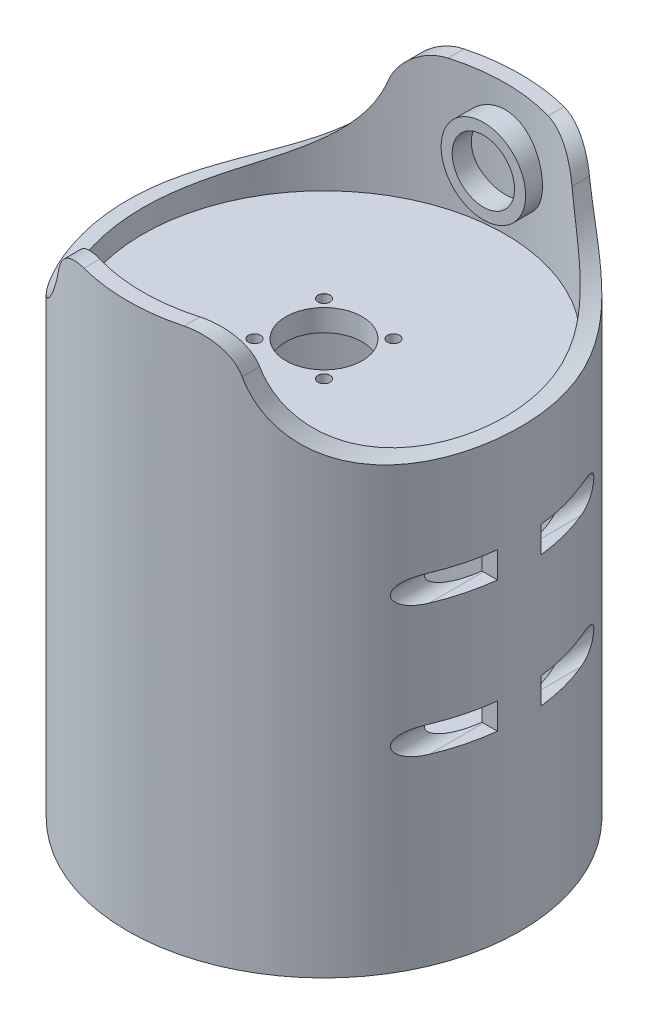
SolidWorks part; units mm, degrees
material "ABS"
ref_plane "Front Plane" through (0, 0, 0) normal (0, 0, 1) x (1, 0, 0)
ref_plane "Top Plane" through (0, 0, 0) normal (0, 1, 0) x (1, 0, 0)
ref_plane "Right Plane" through (0, 0, 0) normal (1, 0, 0) x (0, 0, -1)
sketch "Sketch7" plane through (0, 0, 0) normal (0, 1, 0) x (1, 0, 0)
  circle A0 centre (0, 0) radius 90
  point P0 (0, 0)
  dimension "D1" = 180
extrude "Boss-Extrude3" add sketch "Sketch7" along normal blind 250
sketch "Sketch8" plane through (0, 0, 0) normal (0, 0, 1) x (1, 0, 0)
  line L0 (-83, 210) -> (-83, 90) construction
  line L1 (83, 204) -> (83, 156) construction
  line L2 (90, 250) -> (-90, 250) construction
  line L3 (-90, 250) -> (-90, 0) construction
  line L4 (90, 0) -> (90, 250) construction
  line L5 (-83, 210) -> (-90, 210) construction
  line L6 (83, 210) -> (90, 210) construction
  line L7 (-83, 216) -> (-98, 216)
  line L8 (-98, 216) -> (-98, 204)
  line L9 (-98, 204) -> (-83, 204)
  line L10 (-83, 156) -> (-98, 156)
  line L11 (-98, 156) -> (-98, 144)
  line L12 (-98, 144) -> (-83, 144)
  line L13 (-83, 96) -> (-98, 96)
  line L14 (-98, 96) -> (-98, 84)
  line L15 (-98, 84) -> (-83, 84)
  line L17 (83, 216) -> (105.4044, 174.6914)
  line L18 (83, 204) -> (107.5565, 163.9943)
  line L19 (105.4044, 174.6914) -> (107.5565, 163.9943)
  line L21 (83, 156) -> (116.9139, 117.4845)
  line L22 (83, 144) -> (119.2158, 106.0432)
  line L23 (116.9139, 117.4845) -> (119.2158, 106.0432)
  line L25 (83, 96) -> (128.4235, 60.2777)
  line L26 (83, 84) -> (130.7254, 48.8363)
  line L27 (128.4235, 60.2777) -> (130.7254, 48.8363)
  line L28 (83, 144) -> (83, 96) construction
  arc A0 (-83, 204) -> (-83, 216) centre (-83, 210) ccw
  arc A1 (-83, 144) -> (-83, 156) centre (-83, 150) ccw
  arc A2 (-83, 84) -> (-83, 96) centre (-83, 90) ccw
  arc A3 (83, 216) -> (83, 204) centre (83, 210) ccw
  arc A4 (83, 156) -> (83, 144) centre (83, 150) ccw
  arc A5 (83, 96) -> (83, 84) centre (83, 90) ccw
  dimension "D4" = 12
  dimension "D1" = 40
  dimension "D2" = 7
  dimension "D3" = 15
  dimension "D5" = 40
  dimension "D6" = 60
  dimension "D7" = 60
  dimension "D8" = 60
  dimension "D9" = 15
shell "Shell3" thickness 7 removed face at (0, 250, 90) removed face at (0, 0, 90)
ref_plane "Plane1" through (0, 0, 83) normal (0, 0, -1) x (-1, 0, 0)
sketch "Sketch9" plane through (0, 0, 83) normal (0, 0, -1) x (-1, 0, 0)
  line L0 (83, 250) -> (-83, 250) construction
  circle A0 centre (0, 220) radius 19.3675
  circle A1 centre (0, 220) radius 14.2875
  dimension "D1" = 28.575
  dimension "D2" = 5.08
  dimension "D3" = 30
extrude "Boss-Extrude4" add sketch "Sketch9" along normal blind 10
mirror "Mirror1" about plane through (0, 0, 0) normal (0, 0, 1) of "Boss-Extrude4"
ref_plane "Plane2" through (0, 0, 10) normal (0, 0, 1) x (1, 0, 0)
sketch "Sketch11" plane through (0, 0, 10) normal (0, 0, 1) x (1, 0, 0)
  line L3 (-98, 96) -> (-98, 84)
  line L4 (-98, 84) -> (-83, 84)
  line L5 (-83, 96) -> (-98, 96)
  line L6 (-98, 96) -> (-98, 84)
  line L7 (-98, 84) -> (-83, 84)
  line L8 (-83, 96) -> (-98, 96)
  line L9 (-98, 156) -> (-98, 144)
  line L10 (-98, 144) -> (-83, 144)
  line L11 (-83, 156) -> (-98, 156)
  line L12 (-98, 156) -> (-98, 144)
  line L13 (-98, 144) -> (-83, 144)
  line L14 (-83, 156) -> (-98, 156)
  line L15 (-83, 216) -> (-98, 216)
  line L16 (-98, 216) -> (-98, 204)
  line L17 (-98, 204) -> (-83, 204)
  line L18 (-83, 216) -> (-98, 216)
  line L19 (-98, 216) -> (-98, 204)
  line L20 (-98, 204) -> (-83, 204)
  line L21 (128.4235, 60.2777) -> (83, 96)
  line L22 (130.7254, 48.8363) -> (128.4235, 60.2777)
  line L23 (83, 84) -> (130.7254, 48.8363)
  line L24 (115.4479, 96) -> (83, 96)
  line L25 (115.4479, 84) -> (115.4479, 96)
  line L26 (83, 84) -> (115.4479, 84)
  line L27 (116.9139, 117.4845) -> (83, 156)
  line L28 (119.2158, 106.0432) -> (116.9139, 117.4845)
  line L29 (83, 144) -> (119.2158, 106.0432)
  line L30 (113.0356, 156) -> (83, 156)
  line L31 (113.0356, 144) -> (113.0356, 156)
  line L32 (83, 144) -> (113.0356, 144)
  line L33 (105.4044, 174.6914) -> (83, 216)
  line L34 (83, 204) -> (107.5565, 163.9943)
  line L35 (107.5565, 163.9943) -> (105.4044, 174.6914)
  line L36 (119.1042, 216) -> (83, 216)
  line L37 (83, 204) -> (119.1042, 204)
  line L38 (119.1042, 204) -> (119.1042, 216)
  arc A1 (-83, 84) -> (-83, 96) centre (-83, 90) ccw
  arc A2 (-83, 84) -> (-83, 96) centre (-83, 90) ccw
  arc A3 (-83, 144) -> (-83, 156) centre (-83, 150) ccw
  arc A4 (-83, 144) -> (-83, 156) centre (-83, 150) ccw
  arc A5 (-83, 204) -> (-83, 216) centre (-83, 210) ccw
  arc A6 (-83, 204) -> (-83, 216) centre (-83, 210) ccw
  arc A7 (83, 96) -> (83, 84) centre (83, 90) ccw
  arc A8 (83, 96) -> (83, 84) centre (83, 90) ccw
  arc A9 (83, 156) -> (83, 144) centre (83, 150) ccw
  arc A10 (83, 156) -> (83, 144) centre (83, 150) ccw
  arc A11 (83, 216) -> (83, 204) centre (83, 210) ccw
  arc A12 (83, 216) -> (83, 204) centre (83, 210) ccw
  point P27 (115.4479, 96)
  point P32 (115.4479, 84)
  point P34 (113.0356, 156)
  point P36 (113.0356, 144)
  point P38 (115.4479, 216)
  point P41 (119.1042, 204)
  dimension "D1" = 0
  dimension "D2" = 0
  dimension "D3" = 0
  dimension "D4" = 0
  dimension "D5" = 0
  dimension "D6" = 0
extrude "Cut-Extrude3" cut sketch "Sketch11" along normal through all
mirror "Mirror2" about plane through (0, 0, 0) normal (0, 0, 1) of "Cut-Extrude3"
sketch "Sketch12" plane through (0, 0, 0) normal (0, 1, 0) x (1, 0, 0)
  circle A0 centre (0, 0) radius 90
  circle A1 centre (0, 0) radius 90 construction
extrude "Boss-Extrude5" add sketch "Sketch12" along normal blind 20
ref_plane "Plane3" through (0, 180, 0) normal (0, 1, 0) x (1, 0, 0)
sketch "Sketch14" plane through (0, 180, 0) normal (0, 1, 0) x (1, 0, 0)
  circle A0 centre (0, 0) radius 83
  circle A1 centre (0, 0) radius 83 construction
extrude "Boss-Extrude6" add sketch "Sketch14" along normal blind 10
sketch "Sketch15" plane through (0, 190, 0) normal (0, 1, 0) x (1, 0, 0)
  line L0 (0, 22.5) -> (0, 0) construction
  line L1 (0, 0) -> (15.9099, 15.9099) construction
  circle A0 centre (0, 0) radius 22.5 construction
  circle A1 centre (0, 0) radius 17.5
  dimension "D1" = 45
  dimension "D2" = 45
  dimension "D3" = 35
extrude "Cut-Extrude4" cut sketch "Sketch15" against normal blind 10
hole_wizard "M5 Clearance Hole1" positions "3DSketch1" profile "Sketch17" hole size "M5" standard "ANSI Metric"
sketch3d "3DSketch1"
  point P0 (15.9099, 190, -15.9099)
sketch "Sketch17" plane through (15.9099, 190, -15.9099) normal (1, 0, 0) x (0, 0, 1)
  line L0 (0, 0) -> (0, 11.6524)
  line L1 (0, 11.6524) -> (2.75, 10)
  line L2 (2.75, 10) -> (2.75, 0.025)
  line L3 (2.75, 0.025) -> (2.775, 0)
  line L5 (2.775, 0) -> (0, 0)
  line L6 (-2.75, 0.025) -> (-2.775, 0) construction
  line L10 (0, 11.6524) -> (-2.75, 10) construction
  line L11 (0, -6.35) -> (0, 107.95) construction
  dimension "Hole Dia." = 5.5
  dimension "Hole Depth" = 10
  dimension "Near C'Sink Dia." = 5.55
  dimension "Near C'Sink Angle" = 90
  dimension "Drill Angle" = 118
pattern_circular "CirPattern1" count 4 over 360 about axis through (0, 20, 0) along (0, 1, 0) of "M5 Clearance Hole1"
sketch "Sketch18" plane through (0, 0, 0) normal (0, 0, 1) x (1, 0, 0)
  line L0 (90, 250) -> (-90, 250) construction
  line L1 (-90, 250) -> (-90, 0) construction
  line L2 (-40, 250) -> (-40, 270)
  line L3 (-40, 270) -> (-110, 270)
  line L4 (-110, 270) -> (-110, 200)
  line L5 (-110, 200) -> (-90, 200)
  line L6 (0, 250) -> (0, 180) construction
  line L7 (83, 250) -> (-83, 250) construction
  line L8 (99, 180) -> (-99, 180) construction
  line L9 (110, 200) -> (90, 200)
  line L10 (110, 270) -> (110, 200)
  line L11 (40, 270) -> (110, 270)
  line L12 (40, 250) -> (40, 270)
  arc A0 (-40, 250) -> (-90, 200) centre (-90, 250) cw
  arc A1 (40, 250) -> (90, 200) centre (90, 250) ccw
  dimension "D1" = 50
  dimension "D2" = 20
  dimension "D3" = 20
extrude "Cut-Extrude5" cut sketch "Sketch18" against normal through all both and the other way through all
fillet "Fillet1" radius 20 4 edges at (40, 250, -76.674) (40, 250, 76.674) (-40, 250, 76.674) (-40, 250, -76.674)
